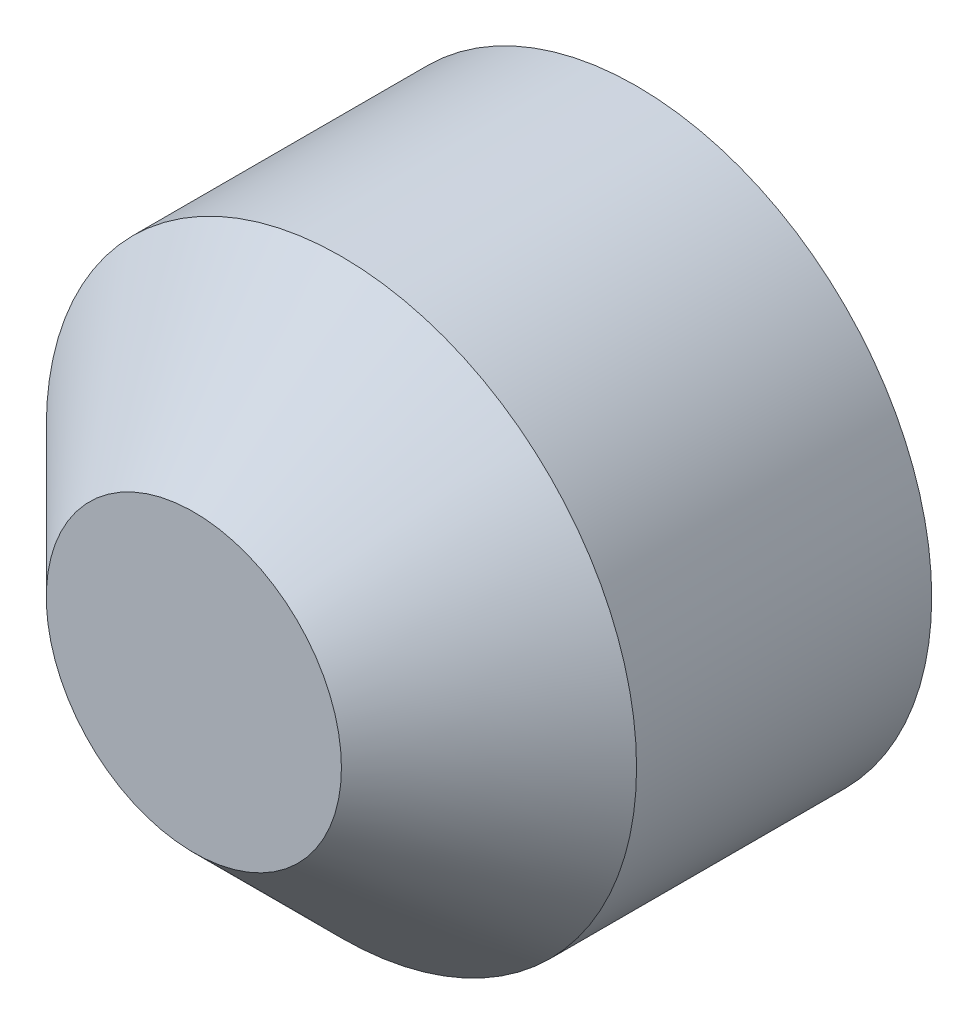
SolidWorks part; units mm, degrees
ref_plane "Front Plane" through (0, 0, 0) normal (0, 0, 1) x (1, 0, 0)
ref_plane "Top Plane" through (0, 0, 0) normal (0, 1, 0) x (1, 0, 0)
ref_plane "Right Plane" through (0, 0, 0) normal (1, 0, 0) x (0, 0, -1)
sketch "Sketch1" plane through (0, 0, 0) normal (1, 0, 0) x (0, 0, -1)
  line L0 (-150, 0) -> (131.7411, 0) construction
  line L1 (0, 0) -> (0, 100)
  line L2 (0, 100) -> (-100, 100)
  line L3 (-100, 100) -> (-150, 50)
  line L4 (-150, 50) -> (-150, 0)
  line L5 (-150, 0) -> (0, 0)
  dimension "D1" = 45
  dimension "base_radius" = 100
  dimension "base_inner_height" = 150
  dimension "base_outer_height" = 100
revolve "Revolve1" add sketch "Sketch1" angle 360 about L0
ref_axis "Axis1" through (0, 0, -7.5) along (0, 0, 1)
